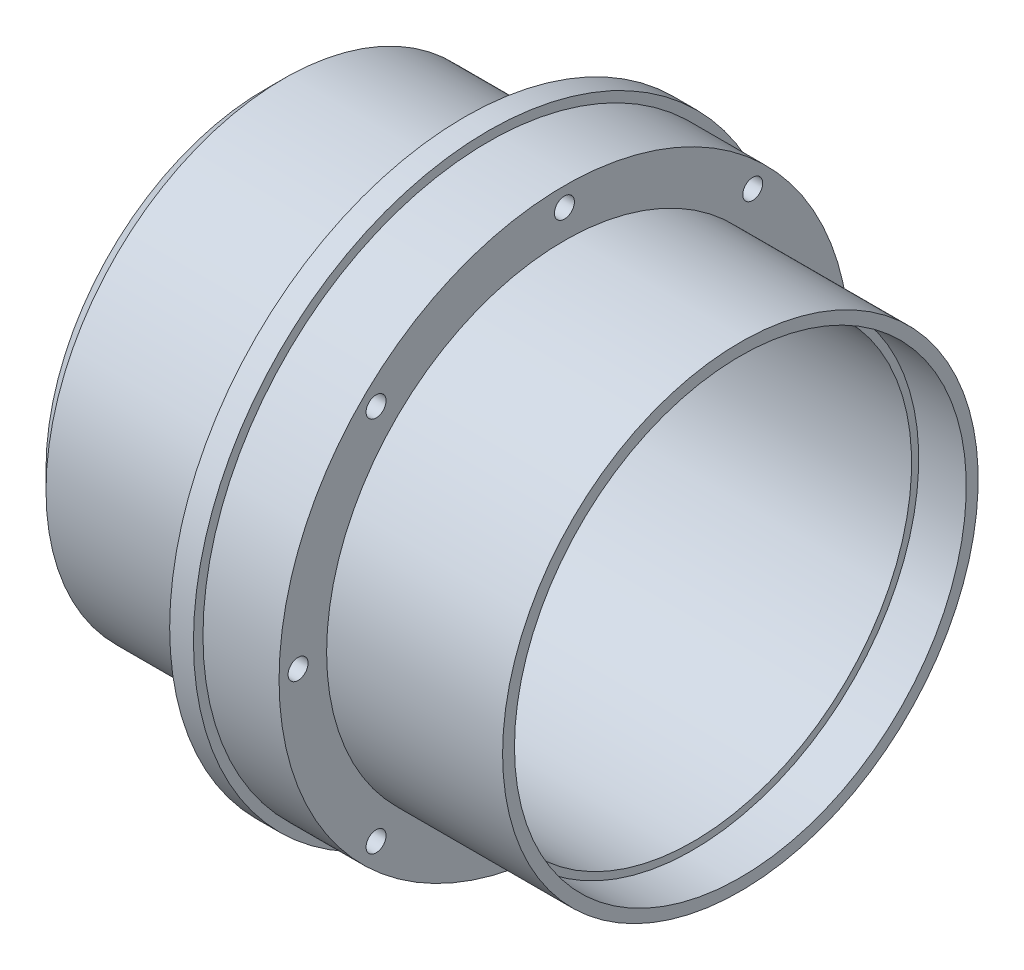
SolidWorks part; units mm, degrees
material "Stop 1060"
ref_plane "Płaszczyzna przednia" through (0, 0, 0) normal (0, 0, 1) x (1, 0, 0)
ref_plane "Płaszczyzna górna" through (0, 0, 0) normal (0, 1, 0) x (1, 0, 0)
ref_plane "Płaszczyzna prawa" through (0, 0, 0) normal (1, 0, 0) x (0, 0, -1)
sketch "Szkic1" plane through (0, 0, 0) normal (0, 0, 1) x (1, 0, 0)
  line L0 (0, 0) -> (55.6647, 0) construction
  line L51 (10, 41) -> (10, 15)
  line L52 (20, 43) -> (12, 43)
  line L53 (40, 50) -> (4, 50)
  line L54 (20, 45) -> (20, 43)
  line L55 (20, 45) -> (30, 45)
  line L56 (30, 45) -> (30, 46)
  line L57 (90, 46) -> (30, 46)
  line L58 (42, 62) -> (42, 52)
  line L59 (47, 62) -> (42, 62)
  line L60 (47, 60) -> (47, 62)
  line L61 (100, 50) -> (63, 50)
  line L62 (47, 60) -> (63, 60)
  line L63 (90, 47.5) -> (90, 46)
  line L64 (90, 47.5) -> (100, 47.5)
  line L65 (100, 47.5) -> (100, 50)
  line L66 (10, 41) -> (12, 43)
  line L67 (40, 50) -> (42, 52)
  line L68 (4, 50) -> (0, 46)
  line L69 (0, 15) -> (10, 15)
  line L70 (63, 50) -> (63, 60)
  line L71 (0, 15) -> (0, 46)
revolve "Obrót1" add sketch "Szkic1" angle 360 about L0
hole_wizard "Otwór gwintowany M51" positions "Szkic2" profile "Szkic4" tap size "M5" standard "DIN" end condition through all
sketch "Szkic2" plane through (42, 0, 0) normal (-1, 0, 0) x (0, 0, 1)
  point P0 (0, 56)
  point P9 (39.598, 39.598)
  point P10 (56, 0)
  point P11 (39.598, -39.598)
  point P12 (0, -56)
  point P13 (-39.598, -39.598)
  point P14 (-56, 0)
  point P15 (-39.598, 39.598)
  dimension "D2" = 8
sketch "Szkic4" plane through (42, 56, 0) normal (0, 1, 0) x (0, 0, 1)
  line L0 (0, 0) -> (0, 58)
  line L1 (0, 58) -> (2.1, 58)
  line L2 (2.1, 58) -> (2.1, 0.425)
  line L3 (2.1, 0.425) -> (2.525, 0)
  line L5 (2.525, 0) -> (0, 0)
  line L6 (-2.1, 0.425) -> (-2.525, 0) construction
  line L11 (0, -6.35) -> (0, 107.95) construction
  dimension "Średnica otworu gwintowanego na wylot" = 4.2
  dimension "Głębokość otworu gwintowanego na wylot" = 58
  dimension "Średnica zewnętrznego pogłębienia stożkowego" = 5.05
  dimension "Kąt zewnętrznego pogłębienia stożkowego" = 90
cosmetic thread "Gwint otworu1" parameters "D2"=5
cosmetic thread "Gwint otworu2" parameters "D2"=5
cosmetic thread "Gwint otworu3" parameters "D2"=5
cosmetic thread "Gwint otworu4" parameters "D2"=5
cosmetic thread "Gwint otworu5" parameters "D2"=5
cosmetic thread "Gwint otworu6" parameters "D2"=5
cosmetic thread "Gwint otworu7" parameters "D2"=5
cosmetic thread "Gwint otworu8" parameters "D2"=5
hole_wizard "Otwór gwintowany M61" positions "Szkic7" profile "Szkic8" tap size "M6" standard "DIN" end condition through all
sketch "Szkic7" plane through (0, 0, 0) normal (-1, 0, 0) x (0, 0, 1)
  point P0 (0, 35)
  point P12 (30.3109, -17.5)
  point P13 (-30.3109, -17.5)
  dimension "D1" = 35
  dimension "D2" = 3
sketch "Szkic8" plane through (0, 35, 0) normal (0, 1, 0) x (0, 0, 1)
  line L0 (0, 0) -> (0, 100)
  line L1 (0, 100) -> (2.5, 100)
  line L2 (2.5, 100) -> (2.5, 0.525)
  line L3 (2.5, 0.525) -> (3.025, 0)
  line L5 (3.025, 0) -> (0, 0)
  line L6 (-2.5, 0.525) -> (-3.025, 0) construction
  line L11 (0, -6.35) -> (0, 107.95) construction
  dimension "Średnica otworu gwintowanego na wylot" = 5
  dimension "Głębokość otworu gwintowanego na wylot" = 100
  dimension "Średnica zewnętrznego pogłębienia stożkowego" = 6.05
  dimension "Kąt zewnętrznego pogłębienia stożkowego" = 90
cosmetic thread "Gwint otworu9" parameters "D2"=6
cosmetic thread "Gwint otworu10" parameters "D2"=6
cosmetic thread "Gwint otworu11" parameters "D2"=6
hole_wizard "Otwór gwintowany M41" positions "Szkic9" profile "Szkic10" tap size "M4" standard "DIN" end condition through all
sketch "Szkic9" plane through (0, 0, 0) normal (-1, 0, 0) x (0, 0, 1)
  point P0 (0, -40)
  point P10 (-34.641, 20)
  point P11 (34.641, 20)
  dimension "D1" = 40
  dimension "D2" = 3
sketch "Szkic10" plane through (0, -40, 0) normal (0, 1, 0) x (0, 0, 1)
  line L0 (0, 0) -> (0, 100)
  line L1 (0, 100) -> (1.65, 100)
  line L2 (1.65, 100) -> (1.65, 0.375)
  line L3 (1.65, 0.375) -> (2.025, 0)
  line L5 (2.025, 0) -> (0, 0)
  line L6 (-1.65, 0.375) -> (-2.025, 0) construction
  line L11 (0, -6.35) -> (0, 107.95) construction
  dimension "Średnica otworu gwintowanego na wylot" = 3.3
  dimension "Głębokość otworu gwintowanego na wylot" = 100
  dimension "Średnica zewnętrznego pogłębienia stożkowego" = 4.05
  dimension "Kąt zewnętrznego pogłębienia stożkowego" = 90
cosmetic thread "Gwint otworu12" parameters "D2"=4
cosmetic thread "Gwint otworu13" parameters "D2"=4
cosmetic thread "Gwint otworu14" parameters "D2"=4
sketch "Szkic11" plane through (0, 0, 0) normal (-1, 0, 0) x (0, 0, 1)
  circle A0 centre (-21.2132, 21.2132) radius 2.5
  circle A1 centre (21.2132, 21.2132) radius 2.5
  circle A2 centre (21.2132, -21.2132) radius 2.5
  circle A3 centre (-21.2132, -21.2132) radius 2.5
  point P12 (0, 0)
  dimension "D2" = 5
  dimension "D1" = 30
  dimension "D3" = 4
extrude "Wytnij-wyciągnięcie1" cut sketch "Szkic11" against normal through all
